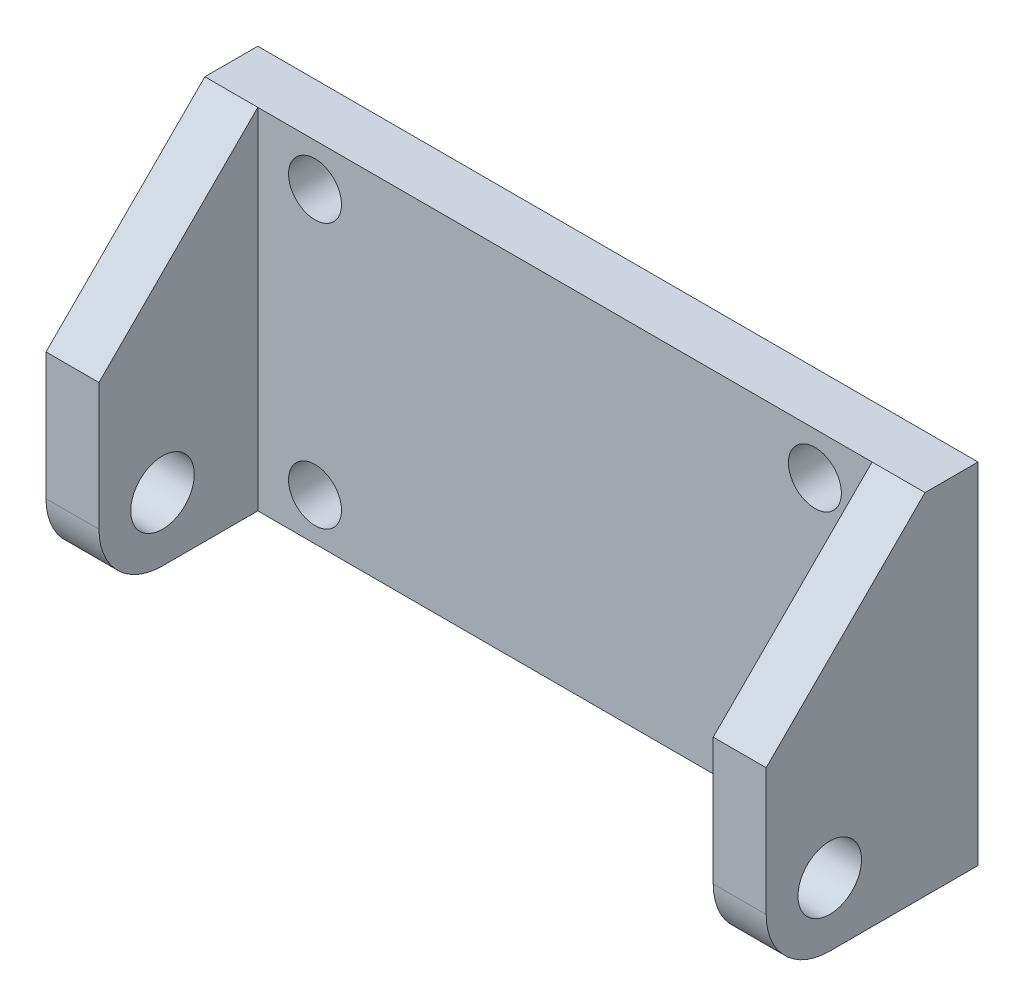
SolidWorks part; units mm, degrees
ref_plane "Front Plane" through (0, 0, 0) normal (0, 0, 1) x (1, 0, 0)
ref_plane "Top Plane" through (0, 0, 0) normal (0, 1, 0) x (1, 0, 0)
ref_plane "Right Plane" through (0, 0, 0) normal (1, 0, 0) x (0, 0, -1)
sketch "Sketch1" plane through (0, 0, 0) normal (0, 0, 1) x (1, 0, 0)
  line L1 (-16.3786, 12.3871) -> (17.6214, 12.3871)
  line L2 (-16.3786, 12.3871) -> (-16.3786, -4.1129)
  line L3 (-16.3786, -4.1129) -> (17.6214, -4.1129)
  line L4 (17.6214, 12.3871) -> (17.6214, -4.1129)
  circle A0 centre (-11.1786, -2.1129) radius 1.25
  circle A1 centre (12.4214, -2.1129) radius 1.25
  circle A2 centre (12.4214, 10.3871) radius 1.25
  circle A3 centre (-11.1786, 10.3871) radius 1.25
  point P6 (0.6214, -4.1129)
  point P8 (0, 0)
  point P9 (0, 0)
  point P15 (0, 0)
  point P16 (0, 0)
  point P17 (0, 0)
  dimension "D3" = 2.5
  dimension "D1" = 11.8
  dimension "D2" = 12.5
  dimension "D4" = 2
  dimension "D5" = 11.8
  dimension "D8" = 2
  dimension "D9" = 34
  dimension "D6" = 2
  dimension "D7" = 2
extrude "Boss-Extrude1" add sketch "Sketch1" along normal blind 2.5
sketch "Sketch2" plane through (0, 0, 2.5) normal (0, 0, 1) x (1, 0, 0)
  line L0 (17.6214, 12.3871) -> (-16.3786, 12.3871) construction
  line L1 (-16.3786, -4.1129) -> (-13.8786, -4.1129)
  line L2 (-16.3786, -4.1129) -> (-16.3786, 12.3871)
  line L3 (-16.3786, 12.3871) -> (-13.8786, 12.3871)
  line L4 (-13.8786, -4.1129) -> (-13.8786, 12.3871)
  line L6 (17.6214, -4.1129) -> (15.1214, -4.1129)
  line L7 (17.6214, -4.1129) -> (17.6214, 12.3871)
  line L8 (17.6214, 12.3871) -> (15.1214, 12.3871)
  line L9 (15.1214, -4.1129) -> (15.1214, 12.3871)
  dimension "D1" = 2.5
  dimension "D2" = 2.5
extrude "Boss-Extrude2" add sketch "Sketch2" along normal blind 7.5
chamfer "Chamfer1" distance 7.5 angle 45 2 edges at (16.3714, 12.3871, 10) (-15.1286, 12.3871, 10)
fillet "Fillet1" radius 3 2 edges at (16.3714, -4.1129, 10) (-15.1286, -4.1129, 10)
sketch "Sketch3" plane through (17.6214, 0, 0) normal (1, 0, 0) x (0, 0, -1)
  line L0 (-7, -4.1129) -> (0, -4.1129) construction
  line L1 (-10, -1.1129) -> (-10, 4.8871) construction
  circle A0 centre (-7, -1.1129) radius 1.5
  dimension "D1" = 3
  dimension "D2" = 3
  dimension "D3" = 3
extrude "Cut-Extrude1" cut sketch "Sketch3" against normal through all
